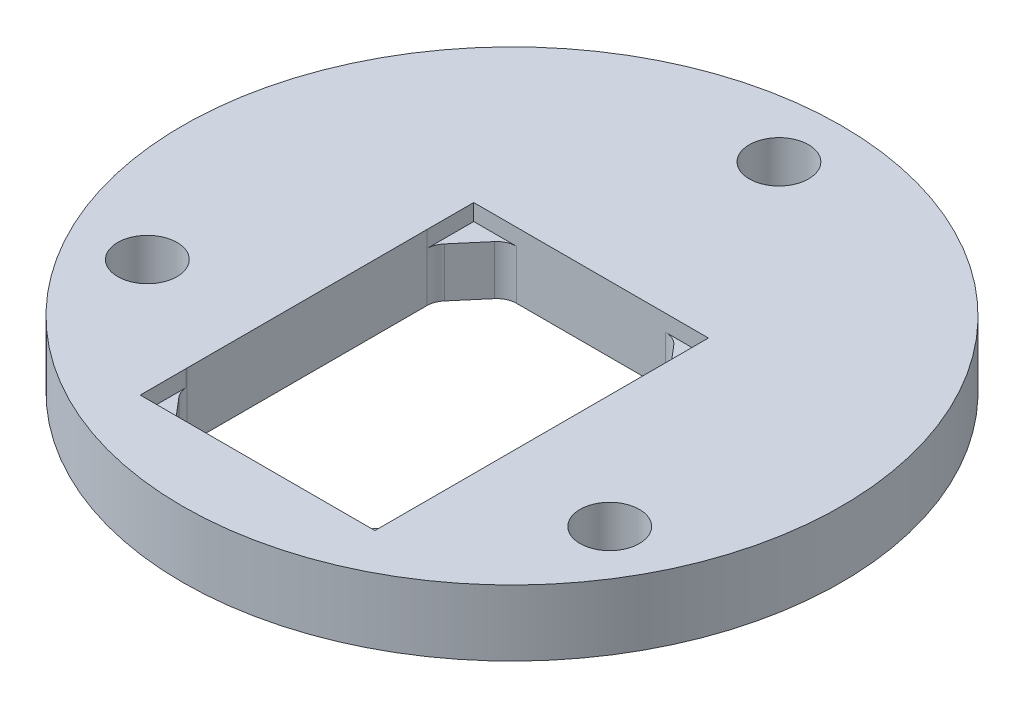
SolidWorks part; units mm, degrees
ref_plane "Front Plane" through (0, 0, 0) normal (0, 0, 1) x (1, 0, 0)
ref_plane "Top Plane" through (0, 0, 0) normal (0, 1, 0) x (1, 0, 0)
ref_plane "Right Plane" through (0, 0, 0) normal (1, 0, 0) x (0, 0, -1)
sketch "Sketch1" plane through (0, 0, 0) normal (0, 1, 0) x (1, 0, 0)
  line L0 (-8.6829, 55.8318) -> (-13.879, 46.8318)
  line L1 (-47.654, -11.6682) -> (-36.6612, -11.6682)
  line L2 (30.2883, -11.6682) -> (25.3542, -3.1221)
  line L3 (-8.6829, 55.8318) -> (-8.6829, 46.8318)
  line L4 (-8.6829, 46.8318) -> (-3.4867, 46.8318)
  line L5 (-8.6829, 46.8318) -> (-13.879, 46.8318)
  line L6 (-36.6612, -11.6682) -> (-42.1576, -2.1482)
  line L7 (-39.4094, -6.9082) -> (-47.654, -11.6682)
  line L8 (25.3542, -3.1221) -> (20.42, -11.6682)
  line L9 (22.8871, -7.3952) -> (30.2883, -11.6682)
  line L10 (30.2883, -11.6682) -> (35.9686, -11.6682)
  line L11 (-47.654, -11.6682) -> (-53.3343, -11.6682)
  line L12 (-8.6829, 55.8318) -> (-8.6829, 60.8318)
  line L13 (-8.6829, 10.8318) -> (-8.6829, 22.8318)
  line L14 (-8.6829, 10.8318) -> (-8.6829, -27.7682)
  line L15 (-8.6829, 22.8318) -> (2.6321, 22.8318)
  line L21 (8.4089, 17.6636) -> (4.9189, 21.7736)
  line L22 (-8.6829, 22.8318) -> (-19.9979, 22.8318)
  line L23 (20.42, -11.6682) -> (30.2883, -11.6682)
  line L24 (-42.1576, -2.1482) -> (-47.654, -11.6682)
  line L25 (-8.6829, -27.7682) -> (-20.0029, -27.7682)
  line L27 (-3.4867, 46.8318) -> (-8.6829, 55.8318)
  line L30 (-25.7773, -22.6128) -> (-22.2873, -26.7128)
  line L31 (-26.4904, 15.7318) -> (-26.4929, -20.6682)
  line L32 (-8.6829, -27.7682) -> (2.6321, -27.7682)
  line L35 (4.9166, -26.7128) -> (8.4066, -22.6128)
  line L36 (9.1221, 15.7218) -> (9.1221, -20.6682)
  line L37 (-25.7741, 17.6774) -> (-22.2816, 21.7772)
  circle A0 centre (-8.6829, 10.8318) radius 60
  circle A1 centre (-8.6829, 10.8318) radius 50
  arc A2 (2.6321, 22.8318) -> (4.9189, 21.7736) centre (2.6321, 19.8318) cw
  arc A3 (9.1221, 15.7218) -> (8.4089, 17.6636) centre (6.1221, 15.7218) ccw
  arc A4 (-19.9979, 22.8318) -> (-22.2816, 21.7772) centre (-19.9979, 19.8318) ccw
  arc A5 (-25.7741, 17.6774) -> (-26.4904, 15.7318) centre (-23.4904, 15.732) ccw
  arc A7 (-26.4929, -20.6678) -> (-25.7773, -22.6128) centre (-23.4929, -20.6682) ccw
  arc A9 (8.4066, -22.6128) -> (9.1221, -20.6682) centre (6.1221, -20.6682) ccw
  arc A11 (4.9189, 21.7736) -> (2.6321, 22.8318) centre (2.6321, 19.8318) ccw
  arc A12 (-22.2873, -26.7128) -> (-20.0029, -27.7682) centre (-20.0029, -24.7682) ccw
  arc A14 (2.6321, -27.7682) -> (4.9166, -26.7128) centre (2.6321, -24.7682) ccw
  dimension "D1" = 120
  dimension "D2" = 100
  dimension "D3" = 12
  dimension "D12" = 3
  dimension "D18" = 6
  dimension "D19" = 6
  dimension "D24" = 3
  dimension "D25" = 3
  dimension "D31" = 6
  dimension "D4" = 60
  dimension "D5" = 9
  dimension "D6" = 60
  dimension "D7" = 60
  dimension "D8" = 38.6
  dimension "D10" = 3
  dimension "D11" = 3
  dimension "D13" = 3
  dimension "D14" = 11.315
  dimension "D15" = 11.315
  dimension "D20" = 11.32
  dimension "D23" = 3
  dimension "D27" = 11.315
  dimension "D32" = 3
  dimension "D34" = 36.39
  dimension "D35" = 3
  dimension "D36" = 3
extrude "Boss-Extrude1" add sketch "Sketch1" along normal blind 10 contours A1
sketch "Sketch2" plane through (0, 10, 0) normal (0, 1, 0) x (1, 0, 0)
  line L0 (-8.6829, -39.1682) -> (-8.6829, -27.7682)
  line L1 (-8.6829, -27.7682) -> (-20.0029, -27.7682)
  line L2 (-20.0029, -27.7682) -> (-20.0029, -24.7682)
  line L3 (-22.2873, -26.7128) -> (-25.7773, -22.6128)
  line L4 (-26.4929, -20.6678) -> (-23.4929, -20.6682)
  line L5 (-26.4929, -20.6678) -> (-26.4904, 15.7318)
  line L6 (-23.4929, -20.6682) -> (-20.0029, -20.6682)
  line L7 (-20.0029, -20.6682) -> (-20.0029, -24.7682)
  line L8 (-25.7741, 17.6774) -> (-22.2816, 21.7772)
  line L9 (-19.9979, 22.8318) -> (2.6321, 22.8318)
  line L10 (4.9189, 21.7736) -> (8.4089, 17.6636)
  line L11 (6.1221, 15.7218) -> (8.4089, 15.7218)
  line L12 (8.4089, 15.7218) -> (8.4089, 17.6636)
  line L13 (9.1221, 15.7218) -> (9.1221, -20.6682)
  line L14 (-8.6829, -27.7682) -> (2.6321, -27.7682)
  line L15 (8.4066, -22.6128) -> (4.9166, -26.7128)
  circle A0 centre (-8.6829, 10.8318) radius 50 construction
  circle A1 centre (-20.0029, -24.7682) radius 3
  circle A3 centre (-23.4929, -20.6682) radius 3
  circle A4 centre (-23.4904, 15.732) radius 3
  circle A5 centre (-19.9979, 19.8318) radius 3
  circle A6 centre (2.6321, 19.8318) radius 3
  circle A7 centre (6.1221, 15.7218) radius 3
  circle A8 centre (6.1221, -20.6682) radius 3
  circle A9 centre (2.6321, -24.7682) radius 3
  dimension "D2" = 6
  dimension "D3" = 6
  dimension "D1" = 7.1
extrude "Cut-Extrude1" cut sketch "Sketch2" against normal blind 35 contours A9 A8 L13 A7 A6 L9 A5 A4 L5 A3 L6 L7 A1 L1 L14 | A5 A4 | A5 A4 | A5 L8 A4 | A4 A5 | A7 A6 | A7 A6 | A7 L10 A6 | A6 A7 | A9 A8 | A9 A8 | A8 A9 | A9 L15 A8 | L6 A3 L4 | A1 A3 L6 L4 | A3 A1 L7 L6 | A3 A1 L2 L7 | L2 A1 L7 | A1 A3 | A3 L3 A1 | A3 region at (-8.6803, 10, 2.4616) region at (-21.2364, 10, 24.941) region at (-18.7296, 10, 24.7682) region at (2.5616, 10, 24.8511) region at (-23.6788, 10, 24.3619) region at (6.3081, 10, 24.3619) region at (4.3771, 10, 22.7182) region at (6.1927, 10, 20.5854) region at (-20.2939, 10, 21.2699) region at (-23.64, 10, 21.876) region at (-21.7479, 10, 22.7182) region at (-23.4928, 10, 19.3949) region at (6.1913, 10, -15.6403) region at (-23.5607, 10, -15.6494) region at (6.3086, 10, -19.4169) region at (4.3771, 10, -17.7768) region at (2.5629, 10, -19.9133) region at (-23.6741, 10, -19.426) region at (-19.9275, 10, -19.9143) region at (-21.7441, 10, -17.7819)
sketch "Sketch3" plane through (0, 10, 0) normal (0, 1, 0) x (1, 0, 0)
  line L0 (-8.6829, 22.8318) -> (9.1171, 22.8318)
  line L1 (9.1171, 22.8318) -> (9.1171, -27.7682)
  line L2 (9.1171, -27.7682) -> (-26.4904, -27.7682)
  line L5 (-26.4904, 22.8318) -> (-26.4904, -27.7682)
  line L6 (-8.6829, 22.8318) -> (-26.4904, 22.8318)
  dimension "D1" = 50.6
  dimension "D3" = 17.8
sketch "Sketch5" plane through (0, 10, 0) normal (0, 1, 0) x (1, 0, 0)
  line L1 (-26.4904, 22.8318) -> (9.1171, 22.8318)
  line L2 (-26.4904, 22.8318) -> (-26.4904, -27.7682)
  line L3 (-26.4904, -27.7682) -> (9.1171, -27.7682)
  line L4 (9.1171, 22.8318) -> (9.1171, -27.7682)
extrude "Cut-Extrude2" cut sketch "Sketch5" against normal blind 2.5
sketch "Sketch7" plane through (0, 10, 0) normal (0, 1, 0) x (1, 0, 0)
  line L0 (-8.6829, 10.8318) -> (-8.6829, 51.3318)
  line L1 (-8.6829, 55.8318) -> (-8.6829, 46.8318) construction
  line L2 (-8.6829, 10.8318) -> (26.3912, -9.4182)
  line L3 (-8.6829, 10.8318) -> (-43.7569, -9.4182)
  circle A0 centre (-8.6829, 10.8318) radius 45
  circle A1 centre (-8.6829, 51.3318) radius 4.5
  circle A2 centre (26.3912, -9.4182) radius 4.5
  circle A3 centre (-43.7569, -9.4182) radius 4.5
  dimension "D5" = 9
  dimension "D6" = 9
  dimension "D7" = 9
  dimension "D1" = 120
  dimension "D2" = 40.5
  dimension "D3" = 40.5
  dimension "D4" = 120
extrude "Cut-Extrude3" cut sketch "Sketch7" against normal blind 10 contours A2
extrude "Cut-Extrude4" cut sketch "Sketch7<3>" against normal blind 10 contours A3
sketch "Sketch7<3>" plane through (0, 10, 0) normal (0, 1, 0) x (1, 0, 0) same geometry as "Sketch7"
extrude "Cut-Extrude5" cut sketch "Sketch7<4>" against normal blind 10 contours A1
sketch "Sketch7<4>" plane through (0, 10, 0) normal (0, 1, 0) x (1, 0, 0) same geometry as "Sketch7"
